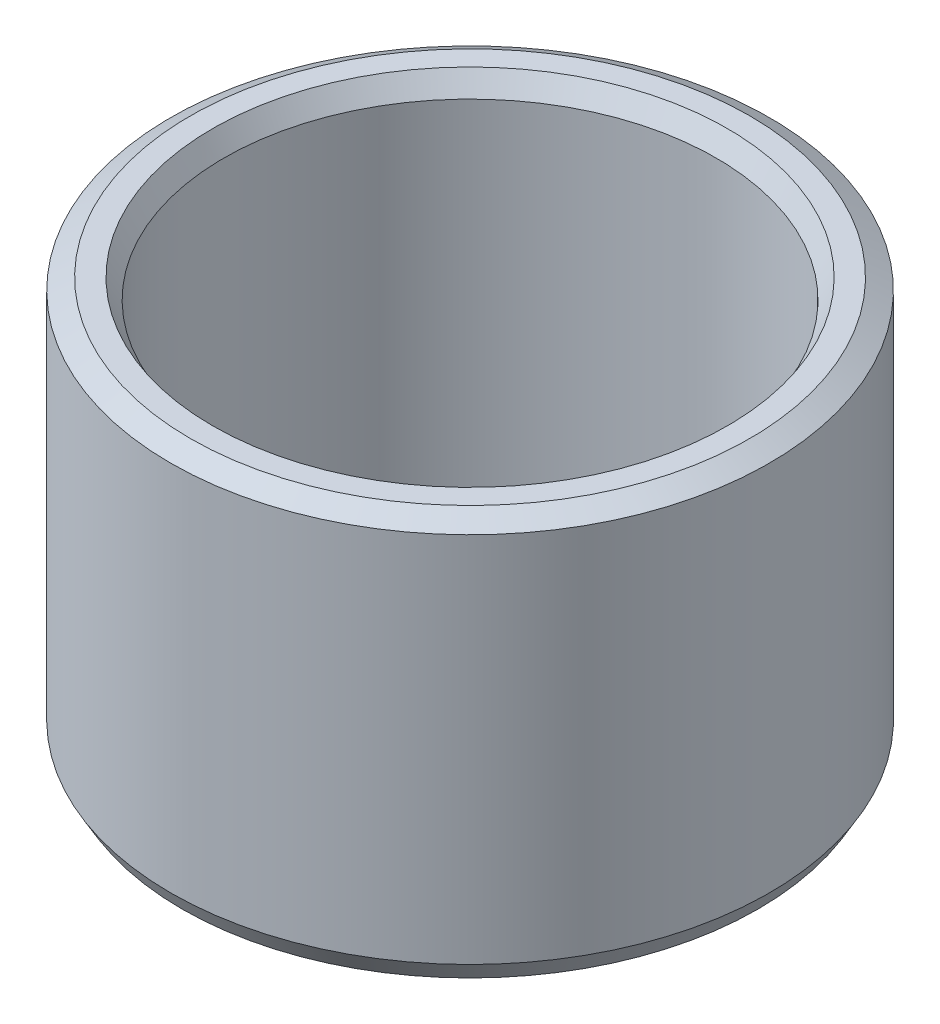
SolidWorks part; units mm, degrees
ref_plane "Front Plane" through (0, 0, 0) normal (0, 0, 1) x (1, 0, 0)
ref_plane "Top Plane" through (0, 0, 0) normal (0, 1, 0) x (1, 0, 0)
ref_plane "Right Plane" through (0, 0, 0) normal (1, 0, 0) x (0, 0, -1)
sketch "Sketch1" plane through (0, 0, 0) normal (0, 1, 0) x (1, 0, 0)
  circle A0 centre (0, 0) radius 50
  dimension "SLEEVE_OD" = 100
extrude "Boss-Extrude1" add sketch "Sketch1" along normal blind 67.3588
sketch "Sketch2" plane through (0, 0, 0) normal (0, 1, 0) x (1, 0, 0)
  circle A0 centre (0, 0) radius 41.097
  dimension "BORE_D" = 82.1941
extrude "Cut-Extrude1" cut sketch "Sketch2" along normal through all
chamfer "Chamfer1" distance 1.9032 angle 60 4 edges at (0, 67.3588, 41.097) (0, 0, 41.097) (0, 0, 50) (0, 67.3588, 50) first distance on face at (0, 67.3588, 41.097) first distance on face at (0, 0, 41.097) first distance on face at (0, 67.3588, 50)
